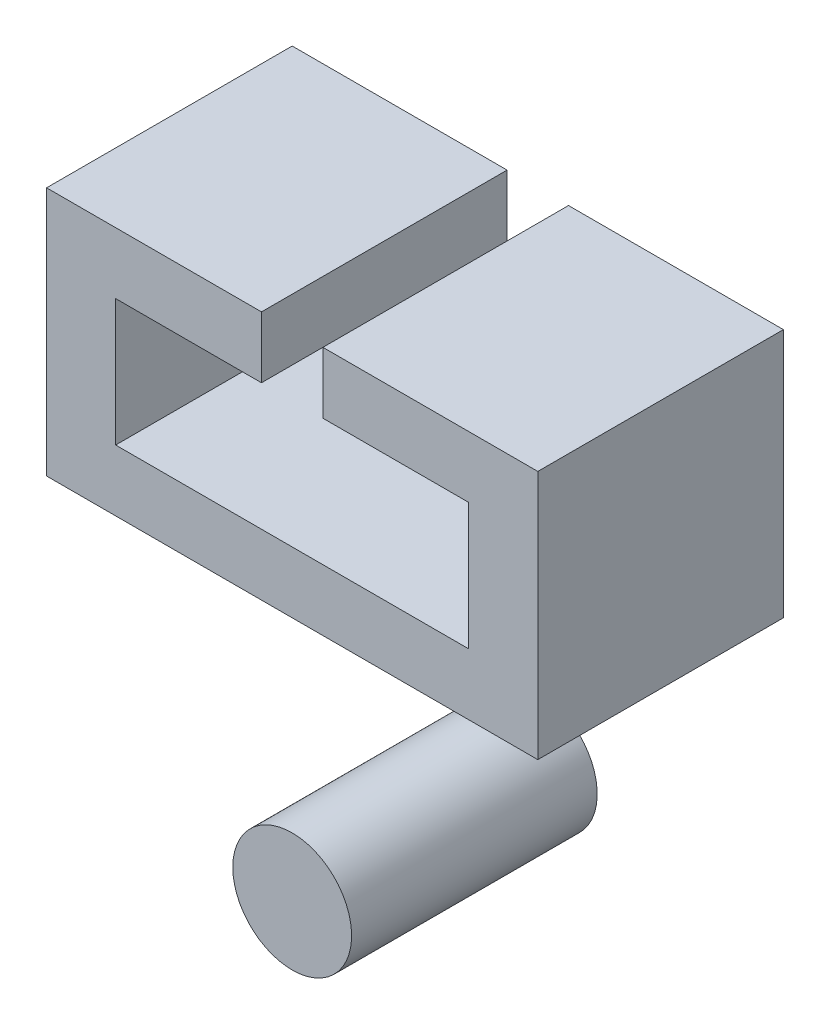
SolidWorks part; units mm, degrees
ref_plane "Front Plane" through (0, 0, 0) normal (0, 0, 1) x (1, 0, 0)
ref_plane "Top Plane" through (0, 0, 0) normal (0, 1, 0) x (1, 0, 0)
ref_plane "Right Plane" through (0, 0, 0) normal (1, 0, 0) x (0, 0, -1)
sketch "Sketch2" plane through (0, 0, 0) normal (0, 0, 1) x (1, 0, 0)
  line L1 (0, 0) -> (101.6, 0)
  line L2 (0, 0) -> (0, 51.6322)
  line L3 (0, 51.6322) -> (101.6, 51.6322)
  line L4 (101.6, 0) -> (101.6, 51.6322)
  dimension "D1" = 101.6
  dimension "D2" = 51.6322
extrude "Boss-Extrude1" add sketch "Sketch2" along normal blind 50.8
sketch "Sketch3" plane through (0, 0, 50.8) normal (0, 0, 1) x (1, 0, 0)
  line L0 (44.45, 51.6322) -> (44.45, 38.9322)
  line L1 (101.6, 51.6322) -> (0, 51.6322) construction
  line L2 (44.45, 38.9322) -> (14.2857, 38.9322)
  line L3 (14.2857, 38.9322) -> (14.2857, 12.7)
  line L4 (14.2857, 12.7) -> (87.3143, 12.7)
  line L5 (87.3143, 12.7) -> (87.3143, 38.9322)
  line L6 (87.3143, 38.9322) -> (57.15, 38.9322)
  line L7 (57.15, 38.9322) -> (57.15, 51.6322)
  line L8 (57.15, 51.6322) -> (44.45, 51.6322)
  line L9 (0, 51.6322) -> (0, 0) construction
  line L10 (101.6, 0) -> (101.6, 51.6322) construction
  line L11 (0, 0) -> (101.6, 0) construction
  point P14 (36.2119, 101.4371)
  point P15 (34.1881, 101.4371)
  point P18 (14.2857, 101.4371)
  point P19 (14.2857, 26.2322)
  dimension "D1" = 14.2857
  dimension "D2" = 14.2857
  dimension "D3" = 12.7
  dimension "D4" = 12.7
  dimension "D5" = 12.7
extrude "Cut-Extrude1" cut sketch "Sketch3" against normal through all
sketch "Sketch4" plane through (0, 0, 0) normal (0, -1, 0) x (1, 0, 0)
  line L0 (0, 0) -> (101.6, 0) construction
  line L1 (44.45, 0) -> (57.15, 0)
  line L2 (44.45, 0) -> (44.45, 4.5161)
  line L3 (44.45, 4.5161) -> (57.15, 4.5161)
  line L4 (57.15, 0) -> (57.15, 4.5161)
  line L5 (101.6, 50.8) -> (101.6, 0) construction
  line L6 (44.45, 0) -> (44.45, 50.8) construction
  line L7 (0, 50.8) -> (101.6, 50.8) construction
  point P6 (-14.955, -5.5912)
  point P7 (-17.8916, 33.452)
  point P11 (-29.8815, 14.7824)
  point P12 (-18.1955, 28.3356)
  point P13 (0, 0)
  point P14 (-6.7497, 41.6927)
  dimension "D1" = 4.5161
  dimension "D2" = 12.7
  dimension "D3" = 44.45
extrude "Boss-Extrude2" add sketch "Sketch4" along normal blind 50.8
sketch "Sketch5" plane through (0, 0, 0) normal (0, 0, -1) x (-1, 0, 0)
  line L0 (-44.45, -50.8) -> (-57.15, -50.8) construction
  circle A0 centre (-50.8, -50.8) radius 12.2868
  dimension "D1" = 24.5735
extrude "Boss-Extrude3" add sketch "Sketch5" against normal blind 50.8 separate body
equation "\"A_length\"= 2in"
equation "\"safety factor\"= 4"
equation "\"yield strength\"= 36000"
equation "\"applied force\"= 800"
equation "\"c length\"= 4in"
equation "\"e length\"= 4in"
equation "\"Area D\"= 0.1"
equation "\"Area B\"= 0.0889"
equation "\"b\"= 0.5in"
equation "\"z\"= 0.0889"
equation "\"DA\"= 0in"
equation "\"Diameter A\"= ( ( 4 * \"z\" ) / pi ) ^ ( 1 / 3 ) * 2"
equation "\"D1@Sketch5\"= \"Diameter A\""
equation "\"b length\"= 2in"
equation "\"d length\"= 2in"
equation "\"thickness b\"= \"Area B\" / \"b\""
equation "\"base D\"= \"Area D\" / \"thickness b\""
equation "\"height c\"= ( \"hc^2*b\" / \"b\" ) ^ ( 1 / 2 )"
equation "\"hc^2*b\"= 0.5333"
equation "\"he ^ 2 *b\"= 1.067"
equation "\"height E\"= ( \"he ^ 2 *b\" / \"b\" ) ^ ( 1 / 2 )"
equation "\"D1@Sketch2\"=\"c length\""
equation "\"D2@Sketch2\"=\"total height\""
equation "\"D1@Sketch3\"=\"base D\""
equation "\"D2@Sketch3\"=\"base D\""
equation "\"total height\" = \"height c\" + \"b\" + \"b\""
equation "\"D3@Sketch3\"=\"b\""
equation "\"D4@Sketch3\"=\"b\""
equation "\"D1@Sketch4\"=\"thickness b\""
equation "\"D2@Sketch4\"=\"b\""
equation "\"D1@Boss-Extrude2\"=\"b length\""
equation "\"D1@Boss-Extrude1\"=\"d length\""
